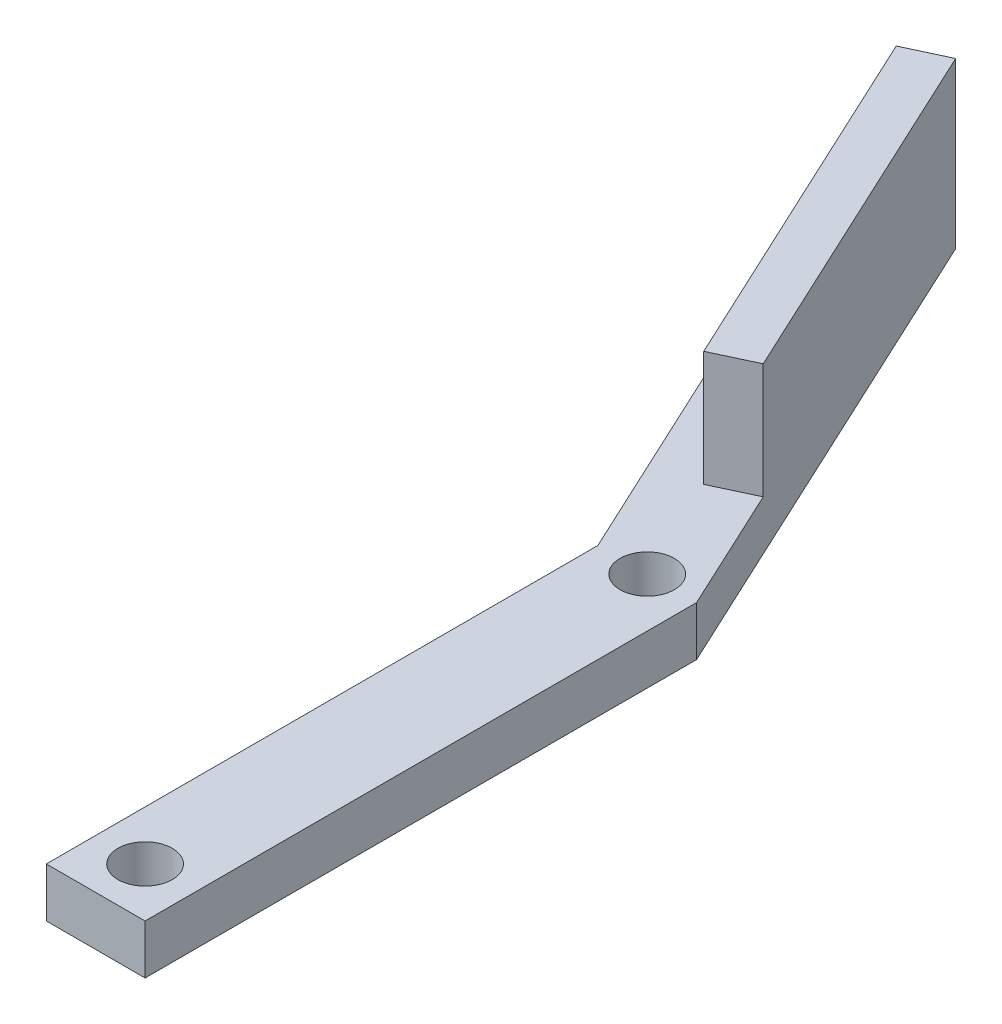
SolidWorks part; units mm, degrees
ref_plane "Front Plane" through (0, 0, 0) normal (0, 0, 1) x (1, 0, 0)
ref_plane "Top Plane" through (0, 0, 0) normal (0, 1, 0) x (1, 0, 0)
ref_plane "Right Plane" through (0, 0, 0) normal (1, 0, 0) x (0, 0, -1)
sketch "Sketch1" plane through (0, 0, 0) normal (0, 1, 0) x (1, 0, 0)
  line L0 (-3, 3) -> (-3, 30.5)
  line L1 (-3, 3) -> (3, 3)
  line L2 (-3, 3) -> (-3, -3)
  line L3 (-3, -3) -> (3, -3)
  line L4 (3, 3) -> (3, -3)
  line L5 (-3, 3) -> (3, -3) construction
  line L6 (-3, -3) -> (3, 3) construction
  line L7 (-3, 30.5) -> (3, 30.5)
  line L8 (3, 30.5) -> (3, 3)
  line L9 (3, 30.5) -> (-10.7502, 59.9874)
  line L10 (-10.7502, 59.9874) -> (-15.6785, 57.6892)
  line L11 (-15.6785, 57.6892) -> (-3, 30.5)
  line L12 (-13.2144, 58.8383) -> (-0.6973, 31.9954)
  line L13 (-3, 36.9335) -> (-0.5358, 38.0826)
  circle A0 centre (0, 0) radius 1.65
  circle A1 centre (0, 30.5) radius 1.65
  dimension "D1" = 3.3
  dimension "D6" = 3.3
  dimension "D2" = 6
  dimension "D3" = 6
  dimension "D4" = 27.5
  dimension "D5" = 205
  dimension "D7" = 30
extrude "Boss-Extrude1" add sketch "Sketch1" along normal blind 3 contours A1 L7 L0 L1 L8 | A1 L7 L9 L10 L11 | L4 L1 L2 L3 A0 | A1 L7 L9 region at (0, 0, -16.4028) region at (0, 0, -2.9151) region at (-8.0976, 0, -44.6356) region at (-0.1852, 0, -34.42)
extrude "Boss-Extrude2" add sketch "Sketch1<4>" along normal blind 10 contours L9 L10 region at (-6.8751, 0, -48.4604)
sketch "Sketch1<4>" plane through (0, 0, 0) normal (0, 1, 0) x (1, 0, 0) same geometry as "Sketch1"
